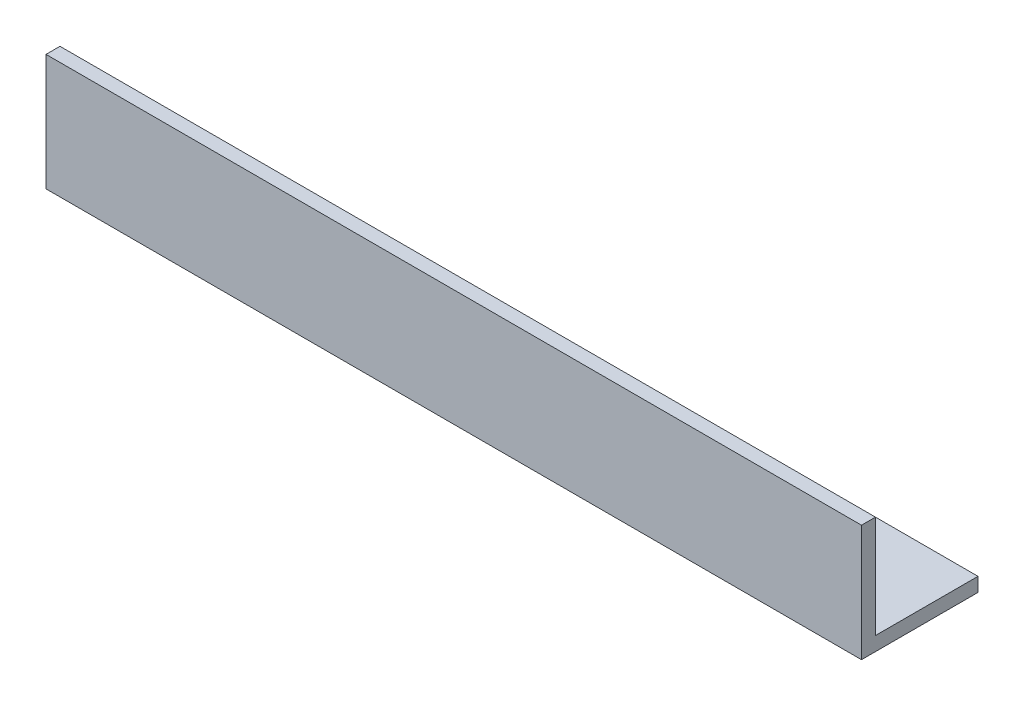
SolidWorks part; units mm, degrees
ref_plane "Спереди" through (0, 0, 0) normal (0, 0, 1) x (1, 0, 0)
ref_plane "Сверху" through (0, 0, 0) normal (0, 1, 0) x (1, 0, 0)
ref_plane "Справа" through (0, 0, 0) normal (1, 0, 0) x (0, 0, -1)
sketch "Эскиз1" plane through (0, 0, 0) normal (1, 0, 0) x (0, 0, -1)
  line L0 (0, 0) -> (50, 0)
  line L5 (0, 50) -> (0, 0)
extrude "Вытянуть-Тонкостенный2" add sketch "Эскиз1" along normal blind 350 thin thin type one direction reverse wall 6
